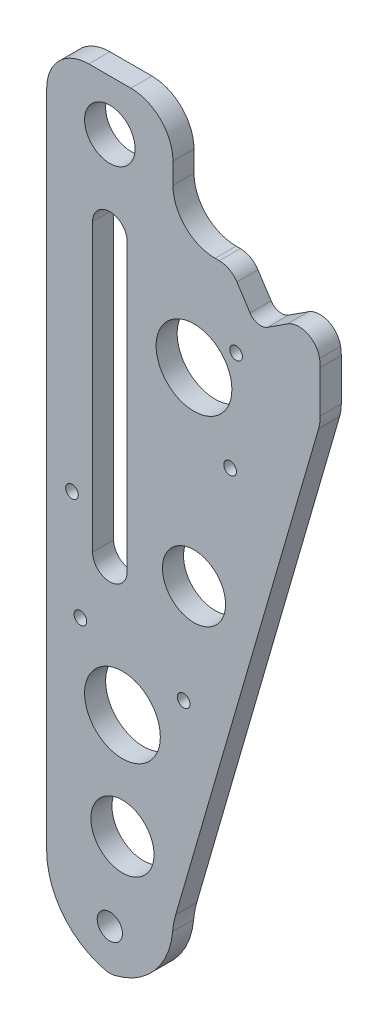
SolidWorks part; units mm, degrees
ref_plane "前视基准面" through (0, 0, 0) normal (0, 0, 1) x (1, 0, 0)
ref_plane "上视基准面" through (0, 0, 0) normal (0, 1, 0) x (1, 0, 0)
ref_plane "右视基准面" through (0, 0, 0) normal (1, 0, 0) x (0, 0, -1)
sketch "草图1" plane through (0, 0, 0) normal (0, 0, 1) x (1, 0, 0)
  line L1 (15, -92.5) -> (-15, -92.5)
  line L2 (15, -92.5) -> (15, 92.5)
  line L3 (15, 92.5) -> (-15, 92.5)
  line L4 (-15, -92.5) -> (-15, 92.5)
  line L5 (15, -92.5) -> (-15, 92.5) construction
  line L6 (15, 92.5) -> (-15, -92.5) construction
  point P0 (0, 0)
  dimension "D1" = 30
  dimension "D2" = 185
extrude "凸台-拉伸1" add sketch "草图1" along normal blind 5
sketch "草图2" plane through (0, 0, 5) normal (0, 0, 1) x (1, 0, 0)
  line L0 (15, 92.5) -> (-15, 92.5) construction
  line L1 (-15, -92.5) -> (15, -92.5) construction
  line L2 (-15, 92.5) -> (-15, -92.5) construction
  circle A0 centre (0, 80.5) radius 6
  circle A1 centre (0, -82.5) radius 3
  dimension "D1" = 12
  dimension "D2" = 12
  dimension "D3" = 6
  dimension "D4" = 10
  dimension "D5" = 15
  dimension "D6" = 15
extrude "切除-拉伸1" cut sketch "草图2" against normal through all
fillet "圆角1" radius 10 2 edges at (-15, 92.5, 2.5) (15, 92.5, 2.5)
sketch "草图5" plane through (0, 0, 5) normal (0, 0, 1) x (1, 0, 0)
  line L0 (15, 67.5) -> (50, 67.5)
  line L1 (15, -92.5) -> (15, 82.5) construction
  line L2 (50, 67.5) -> (50, 37.5)
  line L3 (50, 37.5) -> (15, 37.5)
  line L4 (15, 37.5) -> (15, 67.5)
  line L5 (5, 92.5) -> (-5, 92.5) construction
  dimension "D1" = 30
  dimension "D2" = 35
  dimension "D3" = 25
extrude "凸台-拉伸3" add sketch "草图5" against normal blind 5
fillet "圆角4" radius 10 4 edges at (15, 37.5, 2.5) (50, 37.5, 2.5) (50, 67.5, 2.5) (15, 67.5, 2.5)
fillet "圆角5" radius 18 2 edges at (-15, -92.5, 2.5) (15, -92.5, 2.5)
sketch "草图8" plane through (0, 0, 0) normal (0, 0, -1) x (-1, 0, 0)
  line L0 (-50, 47.5) -> (-50, 57.5) construction
  line L1 (-15, -74.5) -> (-15, 27.5) construction
  line L2 (-5, 92.5) -> (5, 92.5) construction
  line L3 (-4.1, 60.5) -> (-4.1, -7.5)
  line L4 (4.1, -7.5) -> (4.1, 60.5)
  arc A0 (4.1, 60.5) -> (-4.1, 60.5) centre (0, 60.5) ccw
  circle A1 centre (0, 80.5) radius 6 construction
  arc A2 (-4.1, -7.5) -> (4.1, -7.5) centre (0, -7.5) ccw
  dimension "D1" = 20
  dimension "D2" = 50
  dimension "D3" = 8.2
  dimension "D4" = 15
  dimension "D5" = 100
  dimension "D6" = 8.2
extrude "切除-拉伸3" cut sketch "草图8" against normal blind 5 contours L3 A2 L4 A0 region at (0, 26.5, 0)
sketch "草图9" plane through (0, 0, 5) normal (0, 0, 1) x (1, 0, 0)
  line L0 (22.9494, 80.0502) -> (35, 61.5)
  line L1 (35, 61.5) -> (47.4959, 69.6177)
  line L2 (40, 67.5) -> (25, 67.5) construction
  line L3 (22.9494, 80.0502) -> (47.4959, 69.6177)
  circle A0 centre (0, 80.5) radius 6 construction
  dimension "D1" = 19
  dimension "D2" = 14.9012
  dimension "D3" = 6
  dimension "D4" = 35
extrude "切除-拉伸4" cut sketch "草图9" against normal blind 5
sketch "草图10" plane through (0, 0, 5) normal (0, 0, 1) x (1, 0, 0)
  line L0 (25, 37.5) -> (40, 37.5) construction
  line L1 (25, 37.5) -> (40, 37.5)
  line L2 (15, -74.5) -> (15, 27.5) construction
  line L3 (15, -74.5) -> (15, 27.5)
  line L4 (15, -74.5) -> (49.6036, 44.7124)
  arc A0 (25, 37.5) -> (15, 27.5) centre (25, 27.5) ccw construction
  arc A1 (25, 37.5) -> (15, 27.5) centre (25, 27.5) ccw
  arc A3 (40, 37.5) -> (50, 47.5) centre (40, 47.5) ccw construction
  arc A4 (40, 37.5) -> (49.6036, 44.7124) centre (40, 47.5) ccw
extrude "凸台-拉伸5" add sketch "草图10" against normal blind 5
sketch "草图11" plane through (0, 0, 5) normal (0, 0, 1) x (1, 0, 0)
  line L0 (-15, 82.5) -> (-15, -74.5) construction
  line L1 (15, -74.5) -> (49.6036, 44.7124) construction
  line L2 (-15, 82.5) -> (-15, -74.5) construction
  circle A0 centre (-7, -22.5) radius 1.5
  circle A1 centre (17.5443, -27.2518) radius 1.5
  circle A2 centre (18.8289, -7.5) radius 1.5
  circle A3 centre (0, -82.5) radius 3 construction
  circle A4 centre (28.5855, 26.1126) radius 1.5
  circle A5 centre (30, 50.5) radius 1.5
  circle A6 centre (-9, 2.5) radius 1.5
  circle A7 centre (0, 80.5) radius 6 construction
  arc A8 (-4.1, -7.5) -> (4.1, -7.5) centre (0, -7.5) ccw construction
  dimension "D1" = 25
  dimension "D2" = 8
  dimension "D3" = 60
  dimension "D4" = 3
  dimension "D5" = 3
  dimension "D6" = 15
  dimension "D7" = 15
  dimension "D8" = 35
  dimension "D9" = 75
  dimension "D10" = 3
  dimension "D11" = 3
  dimension "D12" = 45
  dimension "D13" = 6
  dimension "D14" = 3
  dimension "D15" = 30
  dimension "D16" = 10
  dimension "D17" = 3
extrude "切除-拉伸5" cut sketch "草图11" against normal through all
sketch "草图12" plane through (0, 0, 5) normal (0, 0, 1) x (1, 0, 0)
  line L0 (-15, 82.5) -> (-15, -74.5) construction
  line L1 (5, 92.5) -> (-5, 92.5) construction
  circle A0 centre (20, 42.5) radius 9
  circle A2 centre (20, -2.5) radius 7.5
  circle A3 centre (3, -37.5) radius 9
  circle A4 centre (3, -62.5) radius 7.5
  circle A5 centre (0, -82.5) radius 3 construction
  dimension "D2" = 18
  dimension "D5" = 35
  dimension "D6" = 50
  dimension "D7" = 15
  dimension "D8" = 35
  dimension "D9" = 95
  dimension "D10" = 18
  dimension "D11" = 18
  dimension "D12" = 130
  dimension "D13" = 18
  dimension "D14" = 15
  dimension "D15" = 20
extrude "切除-拉伸6" cut sketch "草图12" against normal through all
sketch "草图13" plane through (0, 0, 5) normal (0, 0, 1) x (1, 0, 0)
  line L0 (22.8043, 76.6021) -> (34.9571, 57.8947)
  line L1 (34.9571, 57.8947) -> (54.493, 70.5856)
  line L2 (54.493, 70.5856) -> (22.8043, 76.6021)
  line L4 (31.1023, 67.5) -> (35, 61.5) construction
  line L5 (35, 61.5) -> (43.3478, 66.923) construction
  dimension "D1" = 2
  dimension "D2" = 3
extrude "切除-拉伸7" cut sketch "草图13" against normal through all
fillet "圆角9" radius 5 2 edges at (46.3018, 65.2645, 2.5) (28.7173, 67.5, 2.5)
fillet "圆角10" radius 3 1 edges at (34.9571, 57.8947, 2.5)
fillet "圆角11" radius 5 1 edges at (0, -92.2482, 2.5)
fillet "圆角12" radius 20 1 edges at (15, -74.5, 2.5)
